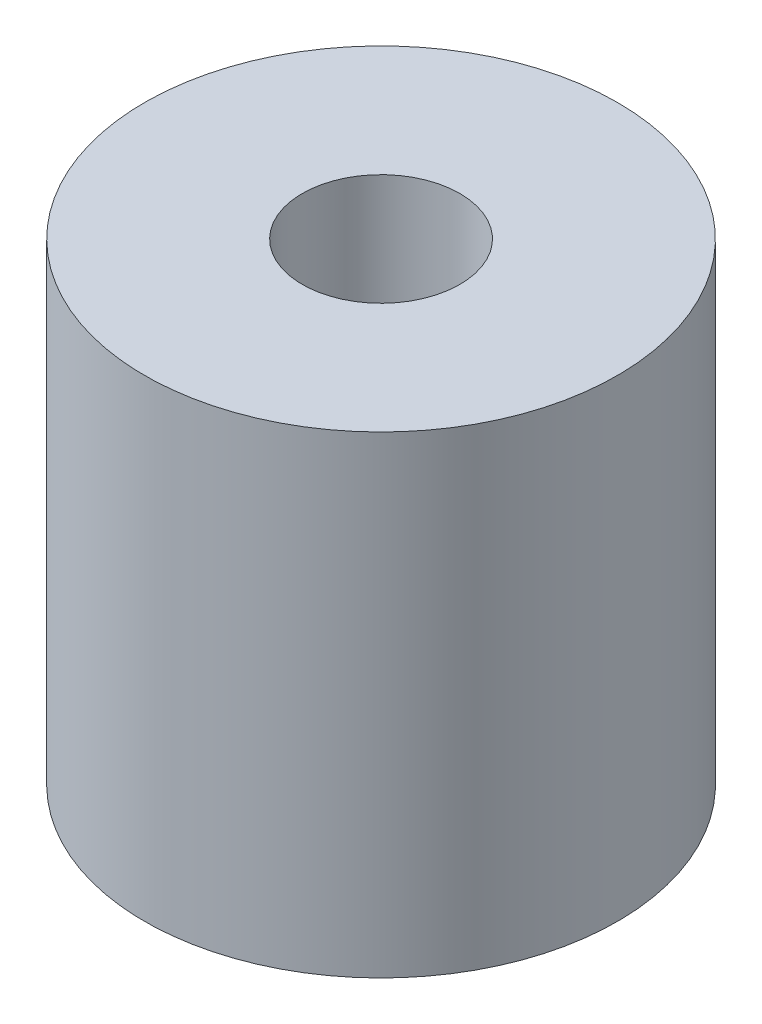
SolidWorks part; units mm, degrees
ref_plane "Спереди" through (0, 0, 0) normal (0, 0, 1) x (1, 0, 0)
ref_plane "Сверху" through (0, 0, 0) normal (0, 1, 0) x (1, 0, 0)
ref_plane "Справа" through (0, 0, 0) normal (1, 0, 0) x (0, 0, -1)
sketch "Эскиз1" plane through (0, 0, 0) normal (0, 0, 1) x (1, 0, 0)
  line L0 (10, 0) -> (10, 60)
  line L1 (10, 60) -> (23.4146, 60)
  line L3 (23.4146, 60) -> (30, 60)
  line L4 (30, 60) -> (30, 0)
  line L5 (30, 0) -> (23.4146, 0)
  line L7 (23.4146, 0) -> (10, 0)
  line L8 (0, -14.7929) -> (0, 77.5948) construction
  point P2 (0, 0)
  point P4 (0, 0)
revolve "Повернуть1" add sketch "Эскиз1" angle 360 about L8
